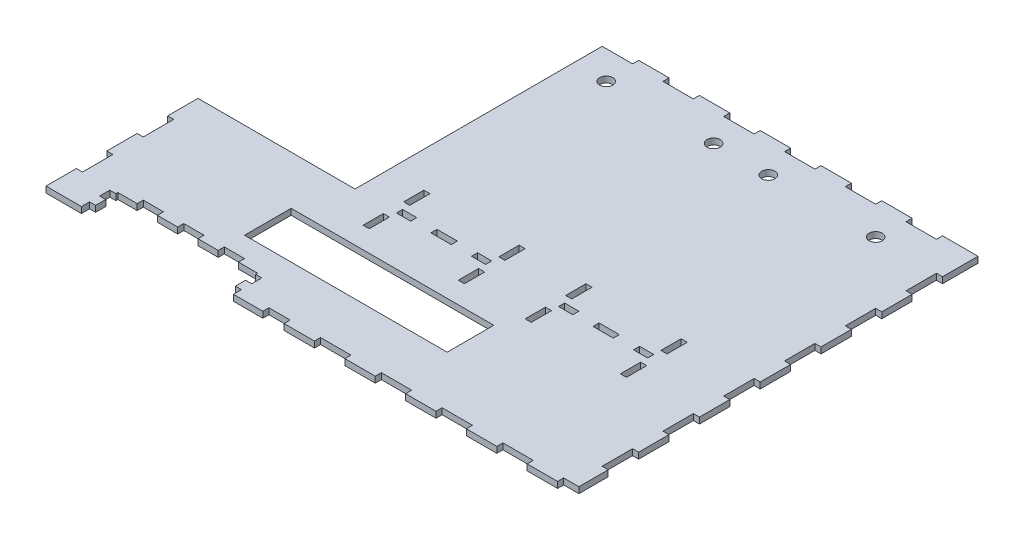
SolidWorks part; units mm, degrees
ref_plane "Alzado" through (0, 0, 0) normal (0, 0, 1) x (1, 0, 0)
ref_plane "Planta" through (0, 0, 0) normal (0, 1, 0) x (1, 0, 0)
ref_plane "Vista lateral" through (0, 0, 0) normal (1, 0, 0) x (0, 0, -1)
sketch "Croquis1" plane through (0, 0, 0) normal (0, 1, 0) x (1, 0, 0)
  line L0 (17.5, 79) -> (20.5, 79)
  line L1 (60, 83) -> (50, 83)
  line L2 (0, 265) -> (17.5, 265) construction
  line L3 (260, 265) -> (260, 247.5)
  line L4 (252.5, 65) -> (237.5, 65)
  line L5 (50, 83) -> (50, 80)
  line L6 (50, 80) -> (40, 80)
  line L7 (40, 80) -> (40, 83)
  line L8 (84.3736, 80) -> (89.5, 80)
  line L9 (40, 83) -> (30, 83)
  line L10 (17.5, 69) -> (20.5, 69)
  line L11 (0, 65) -> (17.5, 65)
  line L12 (92.5, 69) -> (92.5, 65)
  line L13 (20.5, 74) -> (17.5, 74)
  line L14 (92.5, 69) -> (89.5, 69)
  line L15 (30, 83) -> (30, 80)
  line L16 (89.5, 69) -> (89.5, 74)
  line L17 (92.5, 74) -> (92.5, 79)
  line L18 (115, 143) -> (125, 143)
  line L19 (80, 80) -> (84.3736, 80)
  line L20 (89.5, 80) -> (89.5, 79)
  line L21 (30, 80) -> (25.6264, 80)
  line L22 (115, 140) -> (125, 140)
  line L23 (17.5, 69) -> (17.5, 65)
  line L24 (80, 83) -> (80, 80)
  line L25 (89.5, 74) -> (92.5, 74)
  line L26 (70, 83) -> (80, 83)
  line L27 (120, 93) -> (70, 93)
  line L28 (177.5, 65) -> (177.5, 68)
  line L29 (177.5, 68) -> (162.5, 68)
  line L30 (162.5, 68) -> (162.5, 65)
  line L31 (162.5, 65) -> (147.5, 65)
  line L32 (147.5, 65) -> (147.5, 68)
  line L33 (147.5, 68) -> (132.5, 68)
  line L34 (132.5, 68) -> (132.5, 65)
  line L35 (132.5, 65) -> (117.5, 65)
  line L36 (117.5, 65) -> (117.5, 68)
  line L37 (117.5, 68) -> (107, 68)
  line L38 (107, 68) -> (107, 65)
  line L39 (70, 80) -> (70, 83)
  line L40 (92.5, 65) -> (107, 65)
  line L41 (260, 157.5) -> (257, 157.5)
  line L42 (252.5, 68) -> (260, 68)
  line L43 (252.5, 65) -> (252.5, 68)
  line L44 (237.5, 68) -> (237.5, 65)
  line L45 (222.5, 68) -> (237.5, 68)
  line L46 (222.5, 65) -> (222.5, 68)
  line L47 (207.5, 68) -> (207.5, 65)
  line L48 (192.5, 68) -> (207.5, 68)
  line L49 (192.5, 65) -> (192.5, 68)
  line L50 (257, 157.5) -> (257, 142.5)
  line L51 (257, 142.5) -> (260, 142.5)
  line L52 (260, 142.5) -> (260, 127.5)
  line L53 (260, 127.5) -> (257, 127.5)
  line L54 (257, 127.5) -> (257, 112.5)
  line L55 (257, 112.5) -> (260, 112.5)
  line L56 (260, 112.5) -> (260, 97.5)
  line L57 (260, 97.5) -> (257, 97.5)
  line L58 (257, 97.5) -> (257, 82.5)
  line L59 (257, 82.5) -> (260, 82.5)
  line L60 (89.5, 79) -> (92.5, 79)
  line L61 (257, 247.5) -> (260, 247.5)
  line L62 (257, 232.5) -> (257, 247.5)
  line L63 (260, 232.5) -> (257, 232.5)
  line L64 (257, 217.5) -> (260, 217.5)
  line L65 (257, 202.5) -> (257, 217.5)
  line L66 (260, 202.5) -> (257, 202.5)
  line L67 (257, 187.5) -> (260, 187.5)
  line L68 (257, 172.5) -> (257, 187.5)
  line L69 (260, 172.5) -> (257, 172.5)
  line L70 (137.5, 265) -> (137.5, 262)
  line L71 (137.5, 262) -> (152.5, 262)
  line L72 (152.5, 262) -> (152.5, 265)
  line L73 (152.5, 265) -> (167.5, 265)
  line L74 (167.5, 265) -> (167.5, 262)
  line L75 (167.5, 262) -> (182.5, 262)
  line L76 (182.5, 262) -> (182.5, 265)
  line L77 (182.5, 265) -> (197.5, 265)
  line L78 (197.5, 265) -> (197.5, 262)
  line L79 (197.5, 262) -> (212.5, 262)
  line L80 (212.5, 262) -> (212.5, 265)
  line L81 (212.5, 265) -> (227.5, 265)
  line L82 (227.5, 265) -> (227.5, 262)
  line L83 (227.5, 262) -> (242.5, 262)
  line L84 (242.5, 262) -> (242.5, 265)
  line L85 (17.5, 74) -> (17.5, 79)
  line L86 (17.5, 262) -> (17.5, 265) construction
  line L87 (32.5, 262) -> (17.5, 262) construction
  line L88 (32.5, 265) -> (32.5, 262) construction
  line L89 (47.5, 262) -> (47.5, 265) construction
  line L90 (62.5, 262) -> (47.5, 262) construction
  line L91 (62.5, 265) -> (62.5, 262) construction
  line L92 (77.5, 262) -> (77.5, 265) construction
  line L93 (92.5, 262) -> (77.5, 262)
  line L94 (92.5, 265) -> (92.5, 262)
  line L95 (107.5, 262) -> (107.5, 265)
  line L96 (122.5, 262) -> (107.5, 262)
  line L97 (122.5, 265) -> (122.5, 262)
  line L98 (0, 140) -> (3, 140)
  line L99 (3, 140) -> (3, 155) construction
  line L100 (3, 155) -> (0, 155) construction
  line L101 (0, 155) -> (0, 162.5) construction
  line L102 (0, 170) -> (3, 170) construction
  line L103 (3, 170) -> (3, 185) construction
  line L104 (3, 185) -> (0, 185) construction
  line L105 (0, 185) -> (0, 200) construction
  line L106 (0, 200) -> (3, 200) construction
  line L107 (3, 200) -> (3, 215) construction
  line L108 (3, 215) -> (0, 215) construction
  line L109 (0, 215) -> (0, 230) construction
  line L110 (0, 230) -> (3, 230) construction
  line L111 (3, 230) -> (3, 245) construction
  line L112 (3, 245) -> (0, 245) construction
  line L113 (20.5, 69) -> (20.5, 74)
  line L114 (60, 80) -> (70, 80)
  line L115 (60, 83) -> (60, 80)
  line L116 (20.5, 79) -> (20.5, 80)
  line L117 (20.5, 80) -> (25.6264, 80)
  line L118 (70, 93) -> (70, 116)
  line L119 (32.5, 265) -> (47.5, 265) construction
  line L120 (3, 80) -> (0, 80)
  line L121 (3, 95) -> (3, 80)
  line L122 (0, 95) -> (3, 95)
  line L123 (3, 110) -> (0, 110)
  line L124 (3, 125) -> (3, 110)
  line L125 (0, 125) -> (3, 125)
  line L126 (70, 116) -> (170, 116)
  line L127 (170, 116) -> (170, 93)
  line L128 (62.5, 265) -> (77.5, 265) construction
  line L129 (92.5, 265) -> (107.5, 265)
  line L130 (122.5, 265) -> (137.5, 265)
  line L131 (170, 93) -> (120, 93)
  line L132 (195, 143) -> (205, 143)
  line L133 (98, 156.5) -> (98, 146.5)
  line L134 (242.5, 265) -> (260, 265)
  line L135 (0, 245) -> (0, 265) construction
  line L136 (98, 136.5) -> (95, 136.5)
  line L137 (95, 136.5) -> (95, 126.5)
  line L138 (95, 126.5) -> (98, 126.5)
  line L139 (0, 125) -> (0, 140)
  line L140 (0, 95) -> (0, 110)
  line L141 (0, 65) -> (0, 80)
  line L142 (3, 140) -> (77.5, 140)
  line L143 (105, 140) -> (98, 140)
  line L144 (98, 140) -> (98, 143)
  line L145 (98, 143) -> (105, 143)
  line L146 (105, 143) -> (105, 140)
  line L147 (95, 156.5) -> (98, 156.5)
  line L148 (95, 146.5) -> (95, 156.5)
  line L149 (98, 146.5) -> (95, 146.5)
  line L150 (192.5, 65) -> (177.5, 65)
  line L151 (222.5, 65) -> (207.5, 65)
  line L152 (260, 82.5) -> (260, 68)
  line L153 (142, 146.5) -> (145, 146.5)
  line L154 (145, 146.5) -> (145, 156.5)
  line L155 (260, 172.5) -> (260, 157.5)
  line L156 (260, 202.5) -> (260, 187.5)
  line L157 (260, 232.5) -> (260, 217.5)
  line L158 (145, 156.5) -> (142, 156.5)
  line L159 (98, 126.5) -> (98, 136.5)
  line L160 (77.5, 140) -> (77.5, 155)
  line L161 (142, 156.5) -> (142, 146.5)
  line L162 (142, 126.5) -> (142, 136.5)
  line L163 (145, 126.5) -> (142, 126.5)
  line L164 (145, 136.5) -> (145, 126.5)
  line L165 (142, 136.5) -> (145, 136.5)
  line L166 (178, 156.5) -> (178, 146.5)
  line L167 (175, 156.5) -> (178, 156.5)
  line L168 (135, 143) -> (135, 140)
  line L169 (142, 143) -> (135, 143)
  line L170 (142, 140) -> (142, 143)
  line L171 (135, 140) -> (142, 140)
  line L172 (125, 143) -> (125, 140)
  line L173 (115, 140) -> (115, 143)
  line L174 (185, 140) -> (178, 140)
  line L175 (175, 146.5) -> (175, 156.5)
  line L176 (178, 140) -> (178, 143)
  line L177 (178, 146.5) -> (175, 146.5)
  line L178 (222, 146.5) -> (225, 146.5)
  line L179 (225, 146.5) -> (225, 156.5)
  line L180 (222, 140) -> (222, 143)
  line L181 (225, 156.5) -> (222, 156.5)
  line L182 (222, 156.5) -> (222, 146.5)
  line L183 (178, 136.5) -> (175, 136.5)
  line L184 (175, 136.5) -> (175, 126.5)
  line L185 (178, 143) -> (185, 143)
  line L186 (175, 126.5) -> (178, 126.5)
  line L187 (205, 140) -> (205, 143)
  line L188 (185, 143) -> (185, 140)
  line L189 (178, 126.5) -> (178, 136.5)
  line L190 (222, 126.5) -> (222, 136.5)
  line L191 (225, 126.5) -> (222, 126.5)
  line L192 (225, 136.5) -> (225, 126.5)
  line L193 (222, 136.5) -> (225, 136.5)
  line L194 (0, 170) -> (0, 162.5) construction
  line L195 (215, 143) -> (215, 140)
  line L196 (77.5, 155) -> (77.5, 262)
  line L199 (215, 140) -> (222, 140)
  line L200 (195, 140) -> (205, 140)
  line L204 (222, 143) -> (215, 143)
  line L205 (195, 140) -> (195, 143)
  circle A0 centre (173.5, 248) radius 3.25
  circle A1 centre (93.5, 248) radius 3.25
  circle A2 centre (146.5, 248) radius 3.25
  circle A3 centre (226.5, 248) radius 3.25
  dimension "D6" = 10
  dimension "D14" = 6.5
  dimension "D16" = 6.5
  dimension "D7" = 50
  dimension "D8" = 10
  dimension "D9" = 10
  dimension "D10" = 23
  dimension "D11" = 100
  dimension "D13" = 10
  dimension "D18" = 3
  dimension "D19" = 15
  dimension "D20" = 15
  dimension "D21" = 15
  dimension "D22" = 15
  dimension "D23" = 15
  dimension "D25" = 3
  dimension "D26" = 15
  dimension "D27" = 15
  dimension "D28" = 15
  dimension "D29" = 15
  dimension "D30" = 15
  dimension "D31" = 15
  dimension "D32" = 15
  dimension "D34" = 3
  dimension "D35" = 15
  dimension "D36" = 15
  dimension "D37" = 15
  dimension "D38" = 15
  dimension "D39" = 15
  dimension "D40" = 15
  dimension "D41" = 15
extrude "Saliente-Extruir1" add sketch "Croquis1" along normal blind 3
